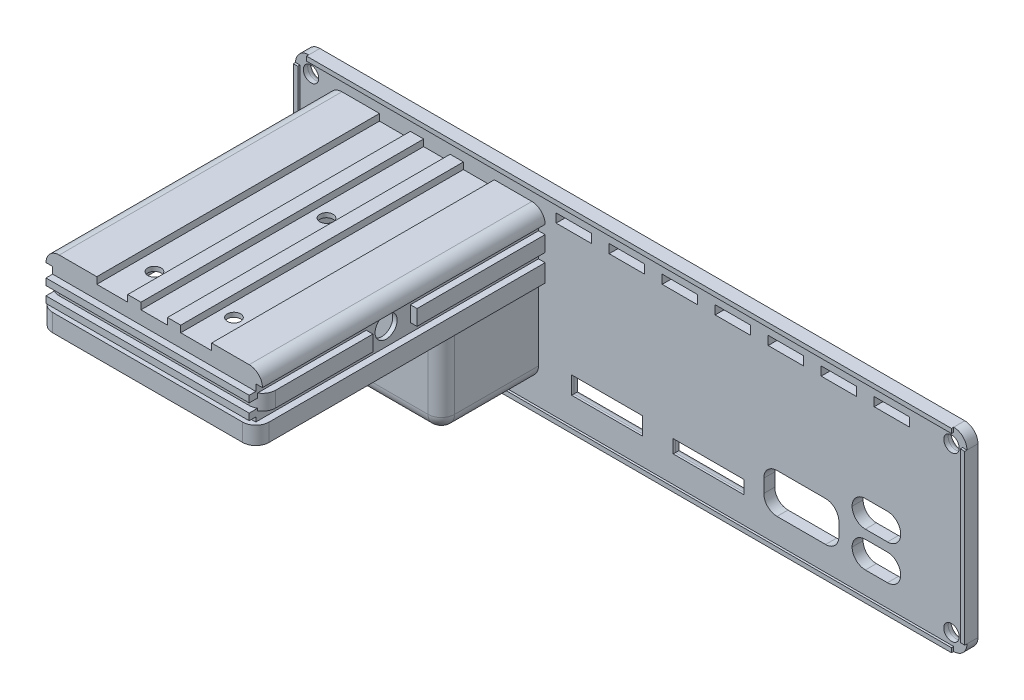
SolidWorks part; units mm, degrees
ref_plane "Front Plane" through (0, 0, 0) normal (0, 0, 1) x (1, 0, 0)
ref_plane "Top Plane" through (0, 0, 0) normal (0, 1, 0) x (1, 0, 0)
ref_plane "Right Plane" through (0, 0, 0) normal (1, 0, 0) x (0, 0, -1)
sketch "Sketch1" plane through (0, 0, 0) normal (0, 0, 1) x (1, 0, 0)
  line L1 (76, -22) -> (-76, -22)
  line L2 (76, -22) -> (76, 22)
  line L3 (76, 22) -> (-76, 22)
  line L4 (-76, -22) -> (-76, 22)
  line L5 (76, -22) -> (-76, 22) construction
  line L6 (76, 22) -> (-76, -22) construction
  point P0 (0, 0)
  dimension "D1" = 152
  dimension "D2" = 44
extrude "main_body" add sketch "Sketch1" along normal blind 2.5
fillet "body_corners" radius 3 4 edges at (-76, -22, 1.25) (76, -22, 1.25) (76, 22, 1.25) (-76, 22, 1.25)
sketch "Sketch2" plane through (0, 0, 2.5) normal (0, 0, 1) x (1, 0, 0)
  line L0 (-76, 18.5) -> (76, 18.5) construction
  line L1 (-76, 19) -> (-76, -19) construction
  line L2 (76, -19) -> (76, 19) construction
  line L3 (-72.5, 22) -> (-72.5, -22) construction
  line L4 (-76, -18.5) -> (76, -18.5) construction
  line L8 (73, 22) -> (-73, 22) construction
  line L9 (72.5, 22) -> (72.5, -22) construction
  line L10 (-73, -22) -> (73, -22) construction
  circle A1 centre (-72.5, -18.5) radius 1.75
  circle A2 centre (72.5, 18.5) radius 1.75
  circle A3 centre (72.5, -18.5) radius 1.75
  circle A4 centre (-72.5, 18.5) radius 1.75
  dimension "D5" = 3.5
  dimension "D6" = 3.5
  dimension "D7" = 3.5
  dimension "D8" = 3.5
  dimension "D1" = 3.5
  dimension "D2" = 3.5
  dimension "D3" = 3.5
  dimension "D4" = 3.5
extrude "mounting_holes" cut sketch "Sketch2" against normal through all
fillet "bolt_heads" radius 1.5 4 edges at (-70.75, -18.5, 0) (-70.75, 18.5, 0) (74.25, -18.5, 0) (74.25, 18.5, 0)
sketch "Sketch3" plane through (0, 0, 2.5) normal (0, 0, 1) x (1, 0, 0)
  line L0 (-76, 5) -> (76, 5) construction
  line L1 (-76, 19) -> (-76, -19) construction
  line L2 (76, -19) -> (76, 19) construction
  line L3 (73, 22) -> (-73, 22) construction
  line L4 (-73, -22) -> (73, -22) construction
  line L5 (0, 22) -> (0, -22) construction
  line L6 (76, -19) -> (76, 19) construction
  line L8 (50, -2) -> (61, -2)
  line L10 (50, -2) -> (50, -8)
  line L11 (50, -8) -> (61, -8)
  line L13 (61, -2) -> (61, -8)
  line L14 (50, -2) -> (61, -8) construction
  line L16 (50, -8) -> (61, -2) construction
  line L17 (30, -6.5) -> (47, -6.5)
  line L18 (30, -6.5) -> (30, -15.5)
  line L19 (30, -15.5) -> (47, -15.5)
  line L20 (47, -6.5) -> (47, -15.5)
  line L21 (30, -6.5) -> (47, -15.5) construction
  line L22 (30, -15.5) -> (47, -6.5) construction
  line L23 (50, -10) -> (61, -10)
  line L24 (50, -10) -> (50, -16)
  line L25 (50, -16) -> (61, -16)
  line L26 (61, -10) -> (61, -16)
  line L27 (50, -10) -> (61, -16) construction
  line L28 (50, -16) -> (61, -10) construction
  line L29 (9.5, -12) -> (25.5, -12)
  line L30 (9.5, -12) -> (9.5, -15)
  line L31 (9.5, -15) -> (25.5, -15)
  line L32 (25.5, -12) -> (25.5, -15)
  line L33 (9.5, -12) -> (25.5, -15) construction
  line L34 (9.5, -15) -> (25.5, -12) construction
  line L35 (-13.5, -11) -> (2.5, -11)
  line L36 (-13.5, -11) -> (-13.5, -15)
  line L37 (-13.5, -15) -> (2.5, -15)
  line L38 (2.5, -11) -> (2.5, -15)
  line L39 (-13.5, -11) -> (2.5, -15) construction
  line L40 (-13.5, -15) -> (2.5, -11) construction
  point P15 (-5.5, -13)
  point P34 (55.5, -13)
  point P36 (55.5, -5)
  point P41 (38.5, -11)
  point P49 (55.5, -16)
  point P51 (17.5, -13.5)
  dimension "D7" = 73.5
  dimension "D8" = 7
  dimension "D9" = 4
  dimension "D10" = 16
  dimension "D12" = 50.5
  dimension "D13" = 6
  dimension "D14" = 11
  dimension "D15" = 29
  dimension "D1" = 17
  dimension "D16" = 6
  dimension "D17" = 15
  dimension "D18" = 15
  dimension "D19" = 11
  dimension "D20" = 6
  dimension "D21" = 17
  dimension "D22" = 9
  dimension "D23" = 8
  dimension "D25" = 14
  dimension "D26" = 6.5
  dimension "D28" = 7
  dimension "D30" = 3
  dimension "D31" = 16
extrude "connectors" cut sketch "Sketch3" against normal through all
fillet "usb_host_corners" radius 3 4 edges at (47, -15.5, 1.25) (47, -6.5, 1.25) (30, -15.5, 1.25) (30, -6.5, 1.25)
fillet "usb_dfu_corners" radius 3 8 edges at (61, -2, 1.25) (61, -8, 1.25) (50, -8, 1.25) (50, -2, 1.25) (61, -10, 1.25) (61, -16, 1.25) (50, -16, 1.25) (50, -10, 1.25)
fillet "sd_rot_corners" radius 2 8 edges at (-5.5, -11, 0) (-13.5, -13, 0) (-5.5, -15, 0) (2.5, -13, 0) (9.5, -13.5, 0) (25.5, -13.5, 0) (17.5, -15, 0) (17.5, -12, 0)
sketch "Sketch4" plane through (0, 0, 2.5) normal (0, 0, 1) x (1, 0, 0)
  line L0 (-76, 19) -> (-76, -19) construction
  line L1 (-67, 17) -> (-21, 17)
  line L2 (-67, 17) -> (-67, -16)
  line L3 (-67, -16) -> (-21, -16)
  line L4 (-21, 17) -> (-21, -16)
  line L5 (-67, 17) -> (-21, -16) construction
  line L6 (-67, -16) -> (-21, 17) construction
  line L7 (-73, -22) -> (73, -22) construction
  point P0 (-44, 0.5)
  dimension "D1" = 9
  dimension "D2" = 6
  dimension "D3" = 33
  dimension "D4" = 46
extrude "keyer" add sketch "Sketch4" along normal blind 22
sketch "Sketch5" plane through (0, 0, 24.5) normal (0, 0, 1) x (1, 0, 0)
  line L0 (-67, -16) -> (-21, 17) construction
  line L1 (-21, 17) -> (-67, 17) construction
  line L2 (-22, -15) -> (-66, -15)
  line L3 (-67, 17) -> (-21, -16) construction
  line L4 (-22, -15) -> (-22, 16)
  line L5 (-22, 16) -> (-66, 16)
  line L6 (-66, -15) -> (-66, 16)
  line L7 (-22, -15) -> (-66, 16) construction
  line L8 (-22, 16) -> (-66, -15) construction
  line L9 (-21, -16) -> (-21, 17) construction
  point P4 (-44, 0.5)
  dimension "D1" = 1
  dimension "D2" = 1
extrude "keyer_cut" cut sketch "Sketch5" along normal blind 24 from offset 25 offset against normal yes
sketch "Sketch6" plane through (0, 0, 0) normal (0, 0, -1) x (-1, 0, 0)
  line L1 (69, -20) -> (-69, -20)
  line L2 (69, -20) -> (69, 20)
  line L3 (69, 20) -> (-69, 20)
  line L4 (-69, -20) -> (-69, 20)
  line L5 (69, -20) -> (-69, 20) construction
  line L6 (69, 20) -> (-69, -20) construction
  point P0 (0, 0)
  dimension "D1" = 138
  dimension "D2" = 40
extrude "paint_slot" cut sketch "Sketch6" against normal blind 0.01
fillet "paint_slot_corners" radius 5 4 edges at (-69, -20, 0.005) (-69, 20, 0.005) (69, -20, 0.005) (69, 20, 0.005)
sketch "Sketch7" plane through (0, 0, 0.01) normal (0, 0, -1) x (-1, 0, 0)
  line L0 (-69, 18) -> (69, 18) construction
  line L1 (-69, 15) -> (-69, -15) construction
  line L2 (69, -15) -> (69, 15) construction
  line L3 (64, 20) -> (-64, 20) construction
  line L4 (-76, -19) -> (-76, 19) construction
  line L5 (-55, 17) -> (-63, 17)
  line L6 (-55, 17) -> (-55, 19)
  line L7 (-55, 19) -> (-63, 19)
  line L8 (-63, 17) -> (-63, 19)
  line L9 (-55, 17) -> (-63, 19) construction
  line L10 (-55, 19) -> (-63, 17) construction
  line L11 (-43, 17) -> (-51, 17)
  line L12 (-43, 17) -> (-43, 19)
  line L13 (-43, 19) -> (-51, 19)
  line L14 (-51, 17) -> (-51, 19)
  line L15 (-43, 17) -> (-51, 19) construction
  line L16 (-43, 19) -> (-51, 17) construction
  line L17 (-31, 17) -> (-39, 17)
  line L18 (-31, 17) -> (-31, 19)
  line L19 (-31, 19) -> (-39, 19)
  line L20 (-39, 17) -> (-39, 19)
  line L21 (-31, 17) -> (-39, 19) construction
  line L22 (-31, 19) -> (-39, 17) construction
  line L23 (-19, 17) -> (-27, 17)
  line L24 (-19, 17) -> (-19, 19)
  line L25 (-19, 19) -> (-27, 19)
  line L26 (-27, 17) -> (-27, 19)
  line L27 (-19, 17) -> (-27, 19) construction
  line L28 (-19, 19) -> (-27, 17) construction
  line L29 (-7, 17) -> (-15, 17)
  line L30 (-7, 17) -> (-7, 19)
  line L31 (-7, 19) -> (-15, 19)
  line L32 (-15, 17) -> (-15, 19)
  line L33 (-7, 17) -> (-15, 19) construction
  line L34 (-7, 19) -> (-15, 17) construction
  line L35 (5, 17) -> (-3, 17)
  line L36 (5, 17) -> (5, 19)
  line L37 (5, 19) -> (-3, 19)
  line L38 (-3, 17) -> (-3, 19)
  line L39 (5, 17) -> (-3, 19) construction
  line L40 (5, 19) -> (-3, 17) construction
  line L41 (17, 17) -> (9, 17)
  line L42 (17, 17) -> (17, 19)
  line L43 (17, 19) -> (9, 19)
  line L44 (9, 17) -> (9, 19)
  line L45 (17, 17) -> (9, 19) construction
  line L46 (17, 19) -> (9, 17) construction
  point P8 (-59, 18)
  point P13 (-47, 18)
  point P18 (-35, 18)
  point P23 (-23, 18)
  point P28 (-11, 18)
  point P33 (1, 18)
  point P38 (13, 18)
  dimension "D1" = 2
  dimension "D2" = 8
  dimension "D3" = 2
  dimension "D4" = 13
  dimension "D5" = 4
  dimension "D6" = 8
  dimension "D7" = 4
  dimension "D8" = 4
  dimension "D9" = 4
  dimension "D10" = 8
  dimension "D11" = 2
  dimension "D12" = 2
  dimension "D13" = 8
  dimension "D14" = 2
  dimension "D15" = 8
  dimension "D16" = 2
  dimension "D17" = 4
  dimension "D18" = 8
  dimension "D19" = 2
  dimension "D20" = 4
  dimension "D21" = 8
  dimension "D22" = 2
extrude "batt_fan_exhaust" cut sketch "Sketch7" against normal through all
sketch "Sketch8" plane through (0, 0, 24.5) normal (0, 0, 1) x (1, 0, 0)
  line L0 (-66, 17) -> (-66, -16) construction
  line L1 (-21, 17) -> (-67, 17) construction
  line L2 (-67, -16) -> (-21, -16) construction
  line L3 (-67, 16) -> (-21, 16) construction
  line L4 (-22, 17) -> (-22, -16) construction
  line L5 (-67, -16) -> (-21, -16) construction
  line L6 (-67, 17) -> (-67, -16) construction
  line L7 (-21, -16) -> (-21, 17) construction
  line L9 (-22, 16) -> (-66, 16)
  line L10 (-22, 16) -> (-22, 5)
  line L11 (-22, 5) -> (-66, 5)
  line L12 (-66, 16) -> (-66, 5)
  dimension "D1" = 1
  dimension "D2" = 1
  dimension "D3" = 1
  dimension "D4" = 11
extrude "back_cut" cut sketch "Sketch8" against normal blind 20
sketch "Sketch9" plane through (0, 0, 24.5) normal (0, 0, 1) x (1, 0, 0)
  line L0 (-21, -16) -> (-21, 17) construction
  line L1 (-67, 17) -> (-21, 17)
  line L2 (-67, 17) -> (-67, 4)
  line L3 (-67, 4) -> (-21, 4)
  line L4 (-21, 17) -> (-21, 4)
  line L6 (-66, 16) -> (-22, 16)
  line L7 (-66, 16) -> (-66, 5)
  line L8 (-66, 5) -> (-22, 5)
  line L9 (-22, 16) -> (-22, 5)
  dimension "D1" = 1
extrude "back_ext" add sketch "Sketch9" along normal blind 42
sketch "Sketch10" plane through (0, 4, 0) normal (0, -1, 0) x (1, 0, 0)
  line L6 (-21, 24.5) -> (-67, 66.5) construction
  line L8 (-22.0952, 65.5) -> (-65.9048, 65.5)
  line L9 (-21, 66.5) -> (-67, 24.5) construction
  line L10 (-22.0952, 65.5) -> (-22.0952, 25.5)
  line L11 (-22.0952, 25.5) -> (-65.9048, 25.5)
  line L12 (-65.9048, 65.5) -> (-65.9048, 25.5)
  line L13 (-22.0952, 65.5) -> (-65.9048, 25.5) construction
  line L14 (-22.0952, 25.5) -> (-65.9048, 65.5) construction
  point P2 (-44, 45.5)
  dimension "D1" = 40
extrude "access_hole" cut sketch "Sketch10" against normal blind 1
sketch "Sketch11" plane through (0, 16, 0) normal (0, -1, 0) x (1, 0, 0)
  line L0 (-22.0952, 65.5) -> (-65.9048, 65.5) construction
  line L5 (-66, 65.5) -> (-22, 65.5)
  line L6 (-66, 65.5) -> (-66, 66.5)
  line L7 (-66, 66.5) -> (-22, 66.5)
  line L8 (-22, 65.5) -> (-22, 66.5)
  line L9 (-67, 66.5) -> (-21, 66.5) construction
  line L10 (-67, 66.5) -> (-67, 24.5) construction
  line L11 (-21, 66.5) -> (-21, 24.5) construction
  dimension "D1" = 1
  dimension "D2" = 1
extrude "back_closer" add sketch "Sketch11" along normal blind 11
sketch "Sketch12" plane through (0, 16, 0) normal (0, -1, 0) x (1, 0, 0)
  line L0 (-65.9048, 57.5) -> (-22, 57.5) construction
  line L1 (-65.9048, 65.5) -> (-65.9048, 25.5) construction
  line L2 (-22, 65.5) -> (-22, 0.01) construction
  line L3 (-44, 65.5) -> (-44, 0) construction
  line L4 (-22.0952, 65.5) -> (-65.9048, 65.5) construction
  line L5 (-73, 0) -> (73, 0) construction
  line L6 (-66, 65.5) -> (-22, 65.5) construction
  circle A0 centre (-52.9524, 57.5) radius 1.5
  circle A1 centre (-34.9524, 57.5) radius 1.5
  circle A2 centre (-44, 27.5) radius 1.5
  point P20 (-43.9524, 57.5)
  dimension "D2" = 3
  dimension "D3" = 3
  dimension "D4" = 3
  dimension "D1" = 8
  dimension "D5" = 9
  dimension "D6" = 9
  dimension "D7" = 30
extrude "paddle_holes" cut sketch "Sketch12" against normal through all
sketch "Sketch13" plane through (0, 16, 0) normal (0, -1, 0) x (1, 0, 0)
  line L0 (-55.9048, 65.5) -> (-55.9048, 25.5) construction
  line L1 (-66, 65.5) -> (-22, 65.5) construction
  line L2 (-65.9048, 25.5) -> (-22.0952, 25.5) construction
  line L3 (-65.9048, 65.5) -> (-65.9048, 25.5) construction
  line L4 (-32.0952, 65.5) -> (-32.0952, 25.5) construction
  line L5 (-22.0952, 25.5) -> (-22.0952, 65.5) construction
  line L6 (-44, 27.5) -> (-55.9048, 27.5) construction
  line L7 (-53.6548, 40) -> (-58.1548, 40)
  line L8 (-53.6548, 40) -> (-53.6548, 34)
  line L9 (-53.6548, 34) -> (-58.1548, 34)
  line L10 (-58.1548, 40) -> (-58.1548, 34)
  line L11 (-53.6548, 40) -> (-58.1548, 34) construction
  line L12 (-53.6548, 34) -> (-58.1548, 40) construction
  line L13 (-29.8452, 40) -> (-34.3452, 40)
  line L14 (-29.8452, 40) -> (-29.8452, 34)
  line L15 (-29.8452, 34) -> (-34.3452, 34)
  line L16 (-34.3452, 40) -> (-34.3452, 34)
  line L17 (-29.8452, 40) -> (-34.3452, 34) construction
  line L18 (-29.8452, 34) -> (-34.3452, 40) construction
  line L19 (-34.9524, 57.5) -> (-52.9524, 57.5) construction
  point P12 (-55.9048, 37)
  point P17 (-32.0952, 37)
  dimension "D1" = 10
  dimension "D2" = 10
  dimension "D3" = 6
  dimension "D4" = 6
  dimension "D5" = 4.5
  dimension "D6" = 4.5
  dimension "D7" = 19.3095
  dimension "D8" = 9.5
  dimension "D9" = 9.5
  dimension "D10" = 20.5
extrude "pilars" add sketch "Sketch13" along normal blind 7
sketch "Sketch14" plane through (-34.3452, 0, 0) normal (-1, 0, 0) x (0, 0, 1)
  line L0 (40, 16) -> (34, 16) construction
  line L1 (34, 9) -> (34, 16) construction
  circle A0 centre (37, 12) radius 1.5
  dimension "D2" = 3
  dimension "D1" = 4
  dimension "D3" = 3
extrude "pilar_hole" cut sketch "Sketch14" against normal blind 47 from offset 33
sketch "Sketch15" plane through (-67, 0, 0) normal (-1, 0, 0) x (0, 0, 1)
  line L0 (37, 12) -> (66.5, 12) construction
  line L1 (66.5, 17) -> (66.5, 4) construction
  circle A0 centre (46, 12) radius 2.5
  circle A1 centre (37, 12) radius 2.5
  dimension "D1" = 5
  dimension "D2" = 5
  dimension "D3" = 9
extrude "adj_holes" cut sketch "Sketch15" against normal blind 1
sketch "Sketch16" plane through (-21, 0, 0) normal (1, 0, 0) x (0, 0, -1)
  circle A0 centre (-37, 12) radius 2.5
  dimension "D1" = 5
extrude "adj_hole1" cut sketch "Sketch16" against normal blind 1
sketch "Sketch17" plane through (0, 17, 0) normal (0, 1, 0) x (1, 0, 0)
  line L0 (-21, -66.5) -> (-67, -66.5) construction
  line L1 (-67, -2.5) -> (-57, -2.5)
  line L2 (-67, -2.5) -> (-67, -66.5)
  line L3 (-67, -66.5) -> (-57, -66.5)
  line L4 (-57, -2.5) -> (-57, -66.5)
  line L5 (-21, -2.5) -> (-67, -2.5) construction
  line L6 (-21, -2.5) -> (-31, -2.5)
  line L7 (-21, -2.5) -> (-21, -66.5)
  line L8 (-21, -66.5) -> (-31, -66.5)
  line L9 (-31, -2.5) -> (-31, -66.5)
  line L10 (-50, -2.5) -> (-47, -2.5)
  line L11 (-50, -2.5) -> (-50, -66.5)
  line L12 (-50, -66.5) -> (-47, -66.5)
  line L13 (-47, -2.5) -> (-47, -66.5)
  line L15 (-38, -2.5) -> (-41, -2.5)
  line L16 (-38, -2.5) -> (-38, -66.5)
  line L17 (-38, -66.5) -> (-41, -66.5)
  line L18 (-41, -2.5) -> (-41, -66.5)
  dimension "D1" = 10
  dimension "D2" = 10
  dimension "D3" = 7
  dimension "D4" = 3
  dimension "D5" = 6
  dimension "D6" = 3
extrude "keyer_bottom_support" add sketch "Sketch17" along normal blind 1.5
sketch "Sketch18" plane through (-67, 0, 0) normal (-1, 0, 0) x (0, 0, 1)
  line L0 (2.5, 18.5) -> (66.5, 18.5) construction
  line L1 (2.5, 18.5) -> (66.5, 18.5)
  line L2 (2.5, 18.5) -> (2.5, 15.5)
  line L3 (2.5, 15.5) -> (66.5, 15.5)
  line L4 (66.5, 18.5) -> (66.5, 15.5)
  line L5 (66.5, 18.5) -> (66.5, 4) construction
  line L6 (66.5, 4) -> (24.5, 4) construction
  line L7 (66.5, 4) -> (2.5, 4)
  line L8 (66.5, 4) -> (66.5, 8)
  line L9 (66.5, 8) -> (2.5, 8)
  line L10 (2.5, 4) -> (2.5, 8)
  line L11 (2.5, 19) -> (2.5, -19) construction
  line L13 (66.5, 13.5) -> (50.5, 13.5)
  line L14 (66.5, 13.5) -> (66.5, 10)
  line L15 (66.5, 10) -> (50.5, 10)
  line L16 (50.5, 13.5) -> (50.5, 10)
  line L17 (2.5, 13.5) -> (32.5, 13.5)
  line L18 (2.5, 13.5) -> (2.5, 10)
  line L19 (2.5, 10) -> (32.5, 10)
  line L20 (32.5, 13.5) -> (32.5, 10)
  dimension "D1" = 4
  dimension "D2" = 3
  dimension "D3" = 64
  dimension "D4" = 2
  dimension "D5" = 3.5
  dimension "D6" = 30
  dimension "D7" = 2
  dimension "D8" = 3.5
  dimension "D9" = 16
extrude "keyer_left_support" add sketch "Sketch18" along normal blind 1.5
sketch "Sketch19" plane through (-21, 0, 0) normal (1, 0, 0) x (0, 0, -1)
  line L0 (-66.5, 4) -> (-66.5, 18.5) construction
  line L1 (-2.5, 18.5) -> (-66.5, 18.5)
  line L2 (-2.5, 18.5) -> (-2.5, 15.5)
  line L3 (-2.5, 15.5) -> (-66.5, 15.5)
  line L4 (-66.5, 18.5) -> (-66.5, 15.5)
  line L5 (-2.5, -19) -> (-2.5, 19) construction
  line L6 (-66.5, 4) -> (-2.5, 4)
  line L7 (-66.5, 4) -> (-66.5, 8)
  line L8 (-66.5, 8) -> (-2.5, 8)
  line L9 (-2.5, 4) -> (-2.5, 8)
  line L10 (-2.5, -16) -> (-2.5, 18.5) construction
  line L11 (-2.5, 13.5) -> (-31.5, 13.5)
  line L12 (-2.5, 13.5) -> (-2.5, 10)
  line L13 (-2.5, 10) -> (-31.5, 10)
  line L14 (-31.5, 13.5) -> (-31.5, 10)
  line L16 (-66.5, 10) -> (-41.5, 10)
  line L17 (-66.5, 10) -> (-66.5, 13.5)
  line L18 (-66.5, 13.5) -> (-41.5, 13.5)
  line L19 (-41.5, 10) -> (-41.5, 13.5)
  dimension "D1" = 3
  dimension "D2" = 4
  dimension "D3" = 2
  dimension "D4" = 3.5
  dimension "D5" = 25
  dimension "D6" = 2
  dimension "D7" = 3.5
  dimension "D8" = 29
extrude "keyer_right_support" add sketch "Sketch19" along normal blind 1.5
sketch "Sketch20" plane through (0, 0, 66.5) normal (0, 0, 1) x (1, 0, 0)
  line L0 (-67, 15.5) -> (-67, 13.5) construction
  line L1 (-67, 14) -> (-21, 14)
  line L2 (-67, 14) -> (-67, 12.5)
  line L3 (-67, 12.5) -> (-21, 12.5)
  line L4 (-21, 14) -> (-21, 12.5)
  line L5 (-21, 8) -> (-21, 10) construction
  line L6 (-67, 15.5) -> (-67, 13.5) construction
  line L7 (-67, 10.5) -> (-21, 10.5)
  line L8 (-67, 10.5) -> (-67, 9)
  line L9 (-67, 9) -> (-21, 9)
  line L10 (-21, 10.5) -> (-21, 9)
  line L11 (-19.5, 8) -> (-19.5, 4) construction
  line L12 (-68.5, 4) -> (-19.5, 4)
  line L13 (-68.5, 4) -> (-68.5, 8)
  line L14 (-68.5, 8) -> (-19.5, 8)
  line L15 (-19.5, 4) -> (-19.5, 8)
  line L16 (-19.5, 4) -> (-19.5, 8) construction
  line L17 (-57, 18.5) -> (-68.5, 18.5) construction
  dimension "D1" = 1
  dimension "D2" = 1.5
  dimension "D3" = 2
  dimension "D4" = 1.5
  dimension "D5" = 4.5
extrude "keyer_back_support" add sketch "Sketch20" along normal blind 1.5
fillet "Fillet1" radius 3 13 edges at (-19.5, 18.5, 34.5) (-68.5, 18.5, 34.5) (-21, -6, 24.5) (-67, -6, 24.5) (-21, -16, 13.5) (-44, -16, 24.5) (-67, -16, 13.5) (-68.5, 6, 68) (-19.5, 6, 68) (-19.5, 11.75, 66.5) (-68.5, 11.75, 66.5) (-22, 10.5, 65.5) (-66, 10.5, 65.5)
fillet "Fillet2" radius 2 7 edges at (-44, 16, 0.01) (-66, 0.5, 0.01) (-44, -15, 0.01) (-22, 0.5, 0.01) (-22, -5, 23.5) (-66, -5, 23.5) (-44, -15, 23.5)
sketch "Sketch21" plane through (0, 0, 2.5) normal (0, 0, 1) x (1, 0, 0)
  line L1 (-73, 22) -> (73, 22)
  line L2 (-73, 22) -> (-73, 21)
  line L3 (-73, 21) -> (73, 21)
  line L4 (73, 22) -> (73, 21)
  line L5 (-73, -22) -> (73, -22)
  line L6 (-73, -22) -> (-73, -21)
  line L7 (-73, -21) -> (73, -21)
  line L8 (73, -22) -> (73, -21)
  line L9 (76, -19) -> (75, -19)
  line L10 (76, -19) -> (76, 19)
  line L11 (76, 19) -> (75, 19)
  line L12 (75, -19) -> (75, 19)
  line L13 (-76, 19) -> (-75, 19)
  line L14 (-76, 19) -> (-76, -19)
  line L15 (-76, -19) -> (-75, -19)
  line L16 (-75, 19) -> (-75, -19)
  dimension "D1" = 1
  dimension "D2" = 1
  dimension "D3" = 38
  dimension "D4" = 1
  dimension "D5" = 146
  dimension "D6" = 1
  dimension "D7" = 38
  dimension "D8" = 146
extrude "mount_spacer" add sketch "Sketch21" along normal blind 0.5
